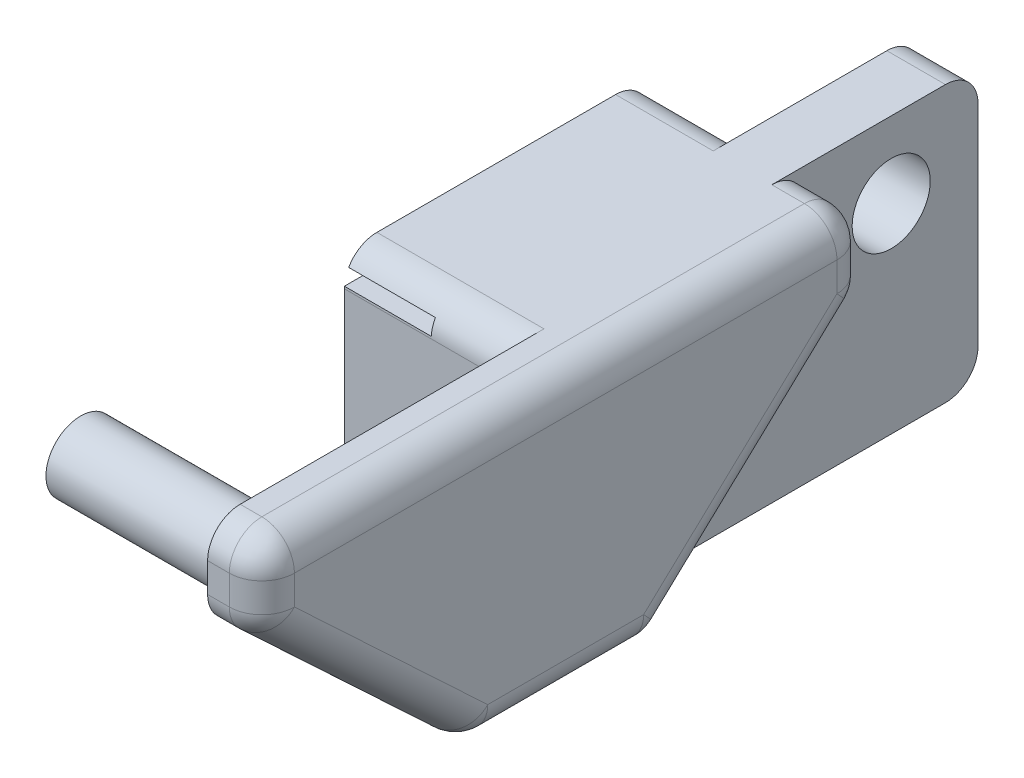
SolidWorks part; units mm, degrees
ref_plane "Front Plane" through (0, 0, 0) normal (0, 0, 1) x (1, 0, 0)
ref_plane "Top Plane" through (0, 0, 0) normal (0, 1, 0) x (1, 0, 0)
ref_plane "Right Plane" through (0, 0, 0) normal (1, 0, 0) x (0, 0, -1)
sketch "Sketch1" plane through (0, 0, 0) normal (0, 1, 0) x (1, 0, 0)
  line L0 (-28.7782, 9.5442) -> (-24.2782, 9.5442)
  line L1 (-24.2782, 9.5442) -> (-24.2782, 17.5442)
  line L2 (-24.2782, 17.5442) -> (-21.5782, 17.5442)
  line L3 (-21.5782, 17.5442) -> (-21.5782, 9.5442)
  line L4 (-21.5782, 9.5442) -> (-18.5782, 9.5442)
  line L5 (-18.5782, 9.5442) -> (-18.5782, -18.4558)
  line L6 (-18.5782, -18.4558) -> (-21.0782, -18.4558)
  line L7 (-21.0782, -18.4558) -> (-21.0782, -4.4558)
  line L10 (-21.0782, -4.4558) -> (-28.7782, -4.4558)
  line L11 (-28.7782, -4.4558) -> (-28.7782, 9.5442)
  dimension "D1" = 10.2
  dimension "D2" = 3
  dimension "D3" = 4.5
  dimension "D4" = 8
  dimension "D5" = 14
  dimension "D6" = 7.7
  dimension "D7" = 36
  dimension "D8" = 8
extrude "Boss-Extrude1" add sketch "Sketch1" along normal blind 12.7
sketch "Sketch2" plane through (-28.7782, 0, 0) normal (-1, 0, 0) x (0, 0, 1)
  line L0 (-17.5442, 12.7) -> (-17.5442, 0)
  line L1 (-17.5442, 0) -> (12.1247, 0)
  line L2 (12.1247, 0) -> (18.4558, 9.2)
  line L3 (18.4558, 9.2) -> (18.4558, 12.7)
  line L4 (18.4558, 12.7) -> (-17.5442, 12.7)
  line L5 (-17.5442, 9.2) -> (18.4558, 9.2) construction
  line L6 (-13.5442, 12.7) -> (-13.5442, 0) construction
  line L7 (-6.2942, 12.7) -> (-6.2942, 0) construction
  line L8 (15.2058, 12.7) -> (15.2058, 4.4773) construction
  line L9 (-9.5442, 3.5481) -> (-3.6573, 0)
  line L11 (4.4558, 0) -> (4.4558, 12.7)
  line L13 (-9.5442, 12.7) -> (-9.5442, 3.5481)
  line L14 (-9.5442, 12.7) -> (4.4558, 12.7)
  line L15 (12.1247, 0) -> (18.4558, 0)
  line L16 (-9.5442, 0) -> (4.4558, 0) construction
  line L17 (-9.5442, 12.7) -> (4.4558, 12.7) construction
  line L18 (-3.6573, 0) -> (4.4558, 0)
  line L19 (-9.5442, 3.5481) -> (-9.5442, 0)
  line L20 (-9.5442, 0) -> (-3.6573, 0)
  line L21 (18.4558, 0) -> (18.4558, 9.2)
  line L22 (15.2058, 10.8) -> (-17.5442, 10.8) construction
  line L23 (-17.5442, 11.3) -> (18.4558, 11.3) construction
  line L25 (18.4558, 11.95) -> (-17.5442, 11.95)
  line L26 (18.4558, 11.95) -> (18.4558, 11.3)
  line L27 (18.4558, 11.3) -> (-17.5442, 11.3)
  line L28 (-17.5442, 11.95) -> (-17.5442, 11.3)
  circle A3 centre (15.2058, 9.2) radius 1.6
  circle A4 centre (-6.2942, 9.2) radius 1.6
  circle A5 centre (-13.5442, 9.2) radius 1.8
  point P35 (-3.6573, 0)
  point P37 (-9.5442, 0)
  point P38 (-9.5442, 3.5481)
  line M18 (-9.5442, 0) -> (4.4558, 0)
  line M21 (-9.5442, 12.7) -> (-9.5442, 0)
  dimension "D9" = 0.5
  dimension "D1" = 12.7
  dimension "D2" = 3.5
  dimension "D3" = 4
  dimension "D4" = 11.25
  dimension "D5" = 8
  dimension "D6" = 6.5
  dimension "D7" = 14
  dimension "D8" = 36
  dimension "D10" = 0.65
extrude "Cut-Extrude2" cut sketch "Sketch2" along direction (1, 0, 0) on the side against the normal up to surface (4.5 mm away) contours L9 M21 M18 region at (-28.7782, 1.1827, -7.5819) up to face at (-24.2782, 6.35, -13.5442)
extrude "Cut-Extrude3" cut sketch "Sketch2<4>" against normal through all contours L15 L21 L2 region at (-28.7782, 3.0667, 16.3454)
sketch "Sketch2<4>" plane through (-28.7782, 0, 0) normal (-1, 0, 0) x (0, 0, 1) same geometry as "Sketch2"
extrude "Boss-Extrude2" add sketch "Sketch2<5>" along normal blind 9.1 from surface contours A3 region at (-28.7782, 9.2, 15.2058) starting at face at (-21.0782, 6.92, 11.5896)
sketch "Sketch2<5>" plane through (-28.7782, 0, 0) normal (-1, 0, 0) x (0, 0, 1) same geometry as "Sketch2"
extrude "Cut-Extrude4" cut sketch "Sketch2<6>" against normal through all contours A5 region at (-28.7782, 9.2, -13.5442)
sketch "Sketch2<6>" plane through (-28.7782, 0, 0) normal (-1, 0, 0) x (0, 0, 1) same geometry as "Sketch2"
extrude "Boss-Extrude3" add sketch "Sketch2<7>" along normal blind 1.4 contours A4 region at (-28.7782, 9.2, -6.2942)
sketch "Sketch2<7>" plane through (-28.7782, 0, 0) normal (-1, 0, 0) x (0, 0, 1) same geometry as "Sketch2"
extrude "Cut-Extrude5" cut sketch "Sketch2<8>" against normal blind 4 from surface contours L25 L28 L27 L26 starting at face at (-28.7782, 9.2, -7.8942)
sketch "Sketch2<8>" plane through (-28.7782, 0, 0) normal (-1, 0, 0) x (0, 0, 1) same geometry as "Sketch2"
sketch "Sketch3" plane through (-18.5782, 0, 0) normal (1, 0, 0) x (0, 0, -1)
  line L0 (9.5442, 12.7) -> (-18.4558, 12.7)
  line L3 (-18.4558, 0) -> (9.5442, 0)
  line L5 (9.5442, 12.7) -> (9.5442, 9.2)
  line L6 (9.5442, 9.2) -> (-0.2708, 0)
  line L7 (-0.2708, 0) -> (-4.4558, 0)
  line L8 (9.5442, 9.2) -> (9.5442, 0)
  line L9 (9.5442, 0) -> (-0.2708, 0)
  line L10 (-4.4558, 12.7) -> (-4.4558, 0)
  line L11 (-18.4558, 0) -> (-8.6408, 0)
  line L12 (-18.4558, 9.2) -> (-18.4558, 0)
  line L13 (-18.4558, 9.2) -> (-8.6408, 0)
  line L14 (-18.4558, 12.7) -> (-18.4558, 9.2)
  point P9 (0, 0)
  line M7 (-18.4558, 9.2) -> (-12.1247, 0)
  line M8 (-12.1247, 0) -> (9.5442, 0)
  line M9 (9.5442, 0) -> (9.5442, 12.7)
  dimension "D1" = 28
  dimension "D2" = 8.37
  dimension "D3" = 9.2
  dimension "D4" = 12.7
extrude "Cut-Extrude6" cut sketch "Sketch3" against normal up to surface (3 mm away) contours L6 L3 M9 | L12 L3 M7 | L13 M7 M8 region at (-18.5782, 3.0667, -6.2725) region at (-18.5782, 3.0667, 16.3454) region at (-18.5782, 3.0667, 13.0738) up to face at (-21.5782, 9.2, -11.7442)
sketch "Sketch4" plane through (0, 0, 0) normal (0, -1, 0) x (1, 0, 0)
  line L0 (-22.9282, -17.5442) -> (-22.9282, 4.4558) construction
  line L1 (-21.5782, -17.5442) -> (-24.2782, -17.5442) construction
  line L2 (-28.7782, 4.4558) -> (-21.0782, 4.4558) construction
  line L4 (-22.1782, -17.5442) -> (-23.6782, -17.5442)
  line L5 (-22.1782, -17.5442) -> (-22.1782, 4.4558)
  line L6 (-22.1782, 4.4558) -> (-23.6782, 4.4558)
  line L7 (-23.6782, -17.5442) -> (-23.6782, 4.4558)
  dimension "D1" = 0.75
  dimension "D2" = 0.75
extrude "Cut-Extrude7" cut sketch "Sketch4" against normal blind 3
sketch "Sketch6" plane through (0, 0, 0) normal (0, -1, 0) x (-1, 0, 0)
  line L1 (23.6782, -4.4558) -> (21.5782, -4.4558)
  line L2 (23.6782, -4.4558) -> (23.6782, -0.2708)
  line L3 (23.6782, -0.2708) -> (21.5782, -0.2708)
  line L4 (21.5782, -4.4558) -> (21.5782, -0.2708)
extrude "Boss-Extrude4" add sketch "Sketch6" against normal blind 1
extrude "Cut-Extrude9" cut sketch "Sketch3<3>" along direction (1, 0, 0) on the side of the normal up to surface (-5.7 mm away) from surface contours L6 L3 M9 region at (-18.5782, 3.0667, -6.2725) up to face at (-24.2782, 9.2, -15.3442) starting at face at (-28.7782, 9.2, -7.8942)
sketch "Sketch3<3>" plane through (-18.5782, 0, 0) normal (1, 0, 0) x (0, 0, -1) same geometry as "Sketch3"
fillet "Fillet3" radius 1.5 19 edges at (-18.5782, 0, 4.4558) (-18.5782, 10.95, 18.4558) (-18.5782, 4.6, 13.5483) (-18.5782, 4.6, -4.6367) (-18.5782, 10.95, -9.5442) (-18.5782, 12.7, 4.4558) (-24.9282, 12.7, 4.4558) (-19.8282, 0, 8.6408) (-19.8282, 9.2, 18.4558) (-19.8282, 12.7, 18.4558) (-26.5282, 0, 0.2708) (-20.0782, 0, 0.2708) (-20.0782, 9.2, -9.5442) (-20.0782, 12.7, -9.5442) (-26.5282, 9.2, -9.5442) (-26.5282, 12.7, -9.5442) (-21.8782, 0, -17.5442) (-23.9782, 0, -17.5442) (-22.9282, 12.7, -17.5442)
fillet "Fillet2" radius 0.25 12 edges at (-23.6782, 0, -7.8867) (-22.1782, 0, -7.8867) (-23.6782, 2.25, -17.5442) (-22.1782, 2.25, -17.5442) (-23.6782, 2, 4.4558) (-22.1782, 2, 4.4558) (-22.9282, 3, -17.5442) (-23.6782, 3, -6.5442) (-22.9282, 3, 4.4558) (-22.1782, 3, -6.5442) (-23.6782, 0.4393, -17.1049) (-22.1782, 0.4393, -17.1049)
